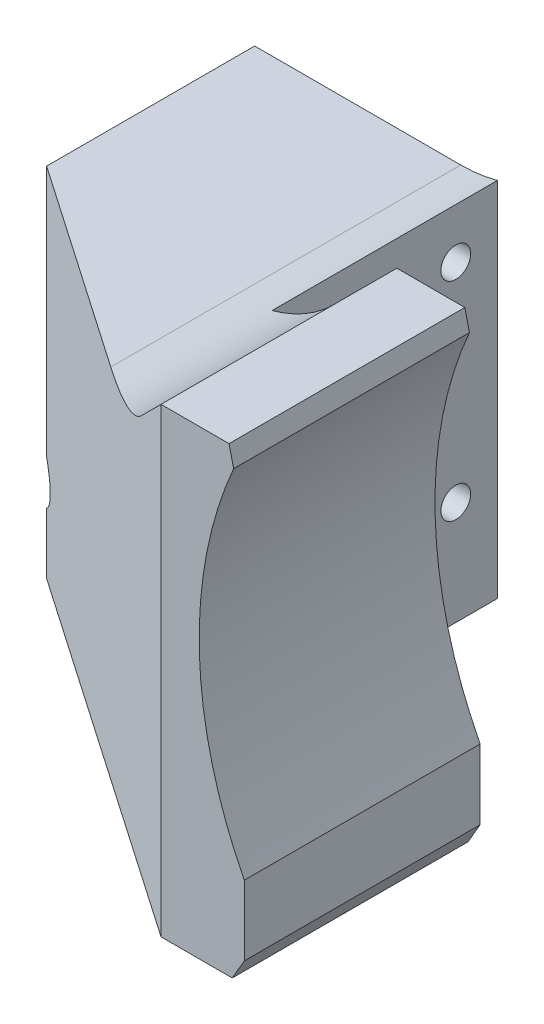
SolidWorks part; units mm, degrees
material "Rubber"
ref_plane "Front Plane" through (0, 0, 0) normal (0, 0, 1) x (1, 0, 0)
ref_plane "Top Plane" through (0, 0, 0) normal (0, 1, 0) x (1, 0, 0)
ref_plane "Right Plane" through (0, 0, 0) normal (1, 0, 0) x (0, 0, -1)
sketch "Sketch1" plane through (0, 0, 0) normal (0, 1, 0) x (1, 0, 0)
  line L0 (0, 0) -> (35, 0)
  line L1 (35, 0) -> (35, -32.5)
  line L2 (35, -32.5) -> (65, -32.5)
  line L3 (65, -32.5) -> (65, -66.5)
  line L4 (65, -66.5) -> (53, -66.5)
  line L5 (53, -66.5) -> (0, -30)
  line L6 (0, -30) -> (0, 0)
  dimension "D1" = 35
  dimension "D2" = 30
  dimension "D3" = 12
  dimension "D4" = 32.5
  dimension "D5" = 34
  dimension "D6" = 30
extrude "Boss-Extrude1" add sketch "Sketch1" along normal blind 51.5
sketch "Sketch3" plane through (35, 0, 0) normal (1, 0, 0) x (0, 0, -1)
  line L2 (-32.5, 0) -> (0, 0) construction
  circle A1 centre (-26.15, 12) radius 5
  dimension "D5" = 10
  dimension "D4" = 12
extrude "Cut-Extrude1" cut sketch "Sketch3" against normal through all
sketch "Sketch4" plane through (0, 0, 0) normal (0, 0, -1) x (-1, 0, 0)
  line L0 (0, 8) -> (-1, 8)
  line L1 (0, 51.5) -> (0, 0) construction
  line L2 (-6, 3) -> (-6, 0)
  line L3 (-35, 0) -> (0, 0) construction
  line L4 (-6, 0) -> (0, 0)
  line L5 (0, 0) -> (0, 8)
  arc A0 (-6, 3) -> (-1, 8) centre (-1, 3) cw
  point P11 (-6, 8)
  dimension "D3" = 5
  dimension "D1" = 8
  dimension "D2" = 6
extrude "Cut-Extrude2" [suppressed] cut sketch "Sketch4" against normal blind 10
sketch "Sketch5" plane through (0, 51.5, 0) normal (0, 1, 0) x (1, 0, 0)
  line L0 (65, -32.5) -> (35, -32.5) construction
  line L1 (65, -66.5) -> (53, -66.5)
  line L2 (65, -66.5) -> (65, -32.5)
  line L3 (65, -32.5) -> (53, -32.5)
  line L4 (53, -66.5) -> (53, -32.5)
extrude "Boss-Extrude2" add sketch "Sketch5" along normal blind 15
chamfer "Chamfer1" distance 15 angle 45 1 edges at (53, 51.5, 49.5)
sketch "Sketch6" plane through (0, 0, 66.5) normal (0, 0, 1) x (1, 0, 0)
  line L0 (65, 66.5) -> (65, 0) construction
  line L1 (53, 0) -> (65, 0) construction
  circle A0 centre (117.5, 40) radius 59
  dimension "D2" = 118
  dimension "D1" = 52.5
  dimension "D3" = 40
extrude "Cut-Extrude3" cut sketch "Sketch6" against normal through all
sketch "Sketch7" plane through (0, 0, 0) normal (-1, 0, 0) x (0, 0, 1)
  line L0 (0, 51.5) -> (0, 0) construction
  line L1 (0, 0) -> (30, 0) construction
  circle A0 centre (6, 15) radius 2.15
  circle A1 centre (6, 45) radius 2.15
  dimension "D1" = 4.3
  dimension "D5" = 4.3
  dimension "D2" = 6
  dimension "D3" = 15
  dimension "D4" = 45
extrude "Cut-Extrude4" cut sketch "Sketch7" against normal through all
sketch "Sketch8" plane through (0, 0, 0) normal (-1, 0, 0) x (0, 0, 1)
  circle A0 centre (6, 45) radius 4.5
  circle A1 centre (6, 15) radius 4.5
  dimension "D1" = 9
  dimension "D2" = 9
extrude "Cut-Extrude5" cut sketch "Sketch8" against normal blind 25
fillet "Fillet1" radius 20 1 edges at (38, 51.5, 44.3349)
chamfer "Chamfer3" distance 3 angle 30 1 edges at (65, 0, 49.5) first distance on face at (65, 6.5394, 49.5)
chamfer "Chamfer4" distance 3 angle 40 1 edges at (64.7861, 66.5, 49.5) first distance on face at (61.6968, 39.7766, 49.5)
